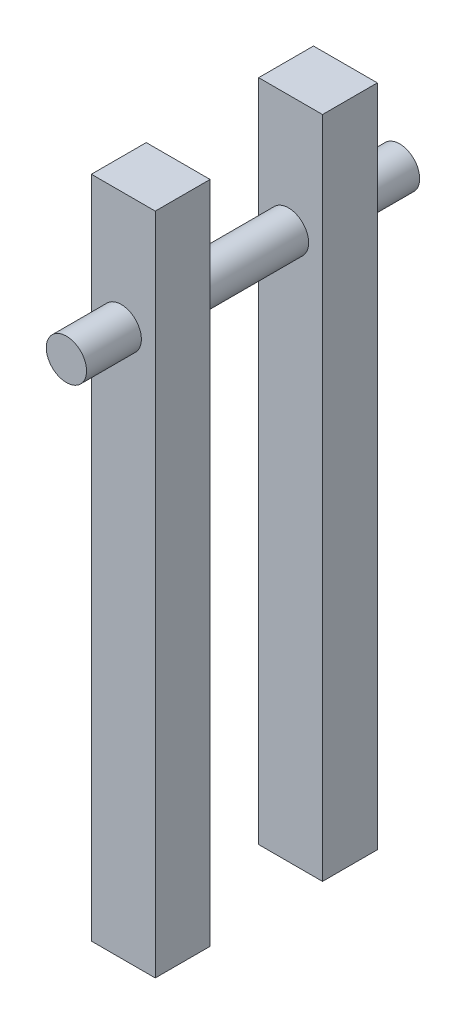
SolidWorks part; units mm, degrees
ref_plane "Front Plane" through (0, 0, 0) normal (0, 0, 1) x (1, 0, 0)
ref_plane "Top Plane" through (0, 0, 0) normal (0, 1, 0) x (1, 0, 0)
ref_plane "Right Plane" through (0, 0, 0) normal (1, 0, 0) x (0, 0, -1)
sketch "Sketch1" plane through (0, 0, 0) normal (1, 0, 0) x (0, 0, -1)
  line L0 (-32.1217, 47.1792) -> (-24.2217, 47.1792)
  line L1 (-8.0217, 47.1792) -> (-0.1217, 47.1792)
  line L2 (-8.0217, 47.1792) -> (-8.0217, -48.5208)
  line L3 (-8.0217, -48.5208) -> (-0.1217, -48.5208)
  line L4 (-0.1217, 47.1792) -> (-0.1217, -48.5208)
  line L5 (-32.1217, 47.1792) -> (-32.1217, -48.5208)
  line L6 (-32.1217, -48.5208) -> (-24.2217, -48.5208)
  line L7 (-24.2217, 47.1792) -> (-24.2217, -48.5208)
  point P8 (0, 0)
  point P9 (0, 0)
  point P10 (0, 0)
  point P11 (0, 0)
  dimension "D1" = 7.9
  dimension "D2" = 95.7
  dimension "D3" = 16.2
extrude "Boss-Extrude1" add sketch "Sketch1" along normal blind 9.2 contours L7 L6 L5 L0
extrude "Boss-Extrude2" add sketch "Sketch1<3>" along normal blind 9.2
sketch "Sketch1<3>" plane through (0, 0, 0) normal (1, 0, 0) x (0, 0, -1) same geometry as "Sketch1"
sketch "Sketch2" plane through (0, 0, 8.0217) normal (0, 0, 1) x (1, 0, 0)
  line L0 (9.2, 47.1792) -> (0, 47.1792) construction
  line L1 (9.2, 47.1792) -> (9.2, -48.5208) construction
  circle A0 centre (4.3, 30.1792) radius 2.9
  dimension "D1" = 5.8
  dimension "D2" = 17
  dimension "D3" = 4.9
extrude "Boss-Extrude3" add sketch "Sketch2" along normal blind 32 and the other way blind 16
